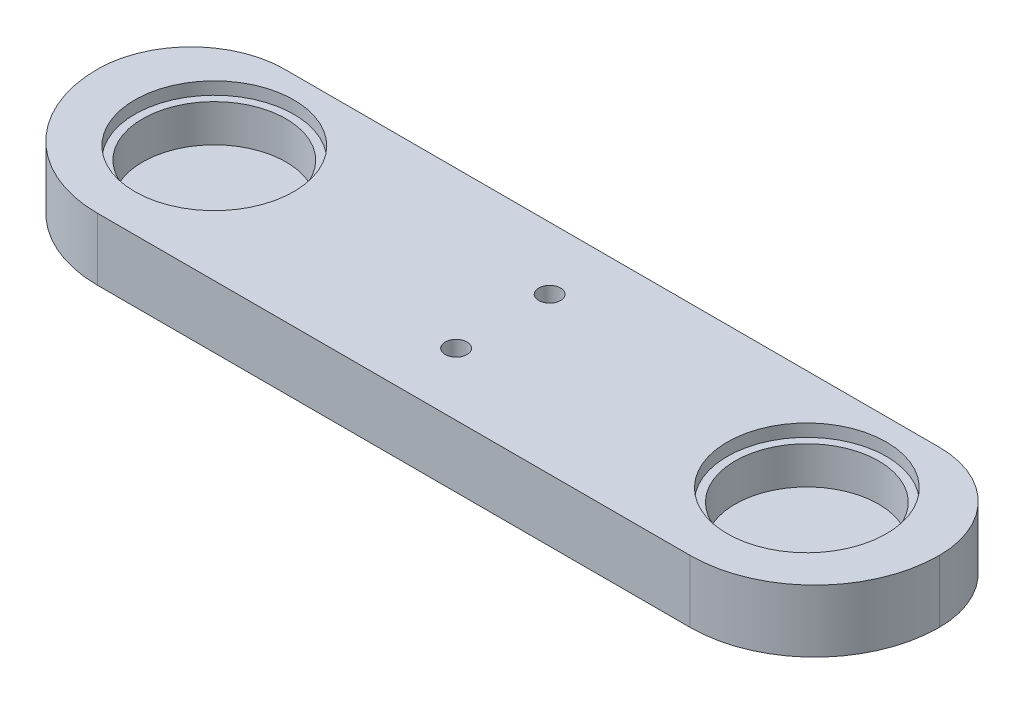
SolidWorks part; units mm, degrees
material "ABS"
ref_plane "Front Plane" through (0, 0, 0) normal (0, 0, 1) x (1, 0, 0)
ref_plane "Top Plane" through (0, 0, 0) normal (0, 1, 0) x (1, 0, 0)
ref_plane "Right Plane" through (0, 0, 0) normal (1, 0, 0) x (0, 0, -1)
sketch "Sketch1" plane through (0, 0, 0) normal (0, 1, 0) x (1, 0, 0)
  line L1 (-47.7502, 9.3769) -> (87.2498, 9.3769)
  line L2 (-47.7502, 9.3769) -> (-47.7502, -25.6231)
  line L3 (-47.7502, -25.6231) -> (87.2498, -25.6231)
  line L4 (87.2498, 9.3769) -> (87.2498, -25.6231)
  dimension "D1" = 35
  dimension "D2" = 135
extrude "Boss-Extrude1" add sketch "Sketch1" along normal blind 10
fillet "Fillet1" radius 20 2 edges at (-47.7502, 5, 25.6231) (87.2498, 5, 25.6231)
sketch "Sketch3" plane through (0, 10, 0) normal (0, 1, 0) x (1, 0, 0)
  line L1 (-47.7502, 9.3769) -> (-47.7502, -5.6231) construction
  line L2 (87.2498, 9.3769) -> (-47.7502, 9.3769) construction
  line L3 (19.7498, 5.0244) -> (19.7498, 27.1098) construction
  circle A0 centre (-27.7502, -6.8863) radius 12.75
  circle A1 centre (67.2498, -6.8863) radius 12.75
  dimension "D1" = 25.5
  dimension "D2" = 20
  dimension "D3" = 16.2632
  dimension "D4" = 67.5
extrude "Cut-Extrude1" cut sketch "Sketch3" against normal blind 2
sketch "Sketch4" plane through (0, 8, 0) normal (0, 1, 0) x (1, 0, 0)
  line L0 (19.7498, -1.4238) -> (19.7498, 28.4625) construction
  line L1 (-47.7502, 9.3769) -> (-47.7502, -5.6231) construction
  circle A0 centre (-27.7502, -6.8863) radius 11.5
  circle A1 centre (67.2498, -6.8863) radius 11.5
  dimension "D1" = 23
  dimension "D2" = 67.5
extrude "Cut-Extrude2" cut sketch "Sketch4" against normal blind 6
sketch "Sketch5" plane through (0, 10, 0) normal (0, 1, 0) x (1, 0, 0)
  line L0 (87.2498, -5.6231) -> (87.2498, 9.3769) construction
  line L1 (87.2498, 9.3769) -> (-47.7502, 9.3769) construction
  circle A0 centre (19.7498, -0.6231) radius 1.75
  circle A1 centre (19.7498, -15.6231) radius 1.75
  dimension "D1" = 3.5
  dimension "D2" = 67.5
  dimension "D3" = 10
  dimension "D4" = 15
extrude "Cut-Extrude3" cut sketch "Sketch5" against normal up to next
sketch "Sketch6" plane through (0, 0, 0) normal (0, -1, 0) x (1, 0, 0)
  circle A0 centre (19.7498, 15.6231) radius 3.1
  circle A1 centre (19.7498, 0.6231) radius 3.1
  dimension "D1" = 6.2
  dimension "D2" = 6.2
extrude "Cut-Extrude4" cut sketch "Sketch6" against normal blind 4
fillet "Fillet2" radius 15 2 edges at (-47.7502, 5, -9.3769) (87.2498, 5, -9.3769)
